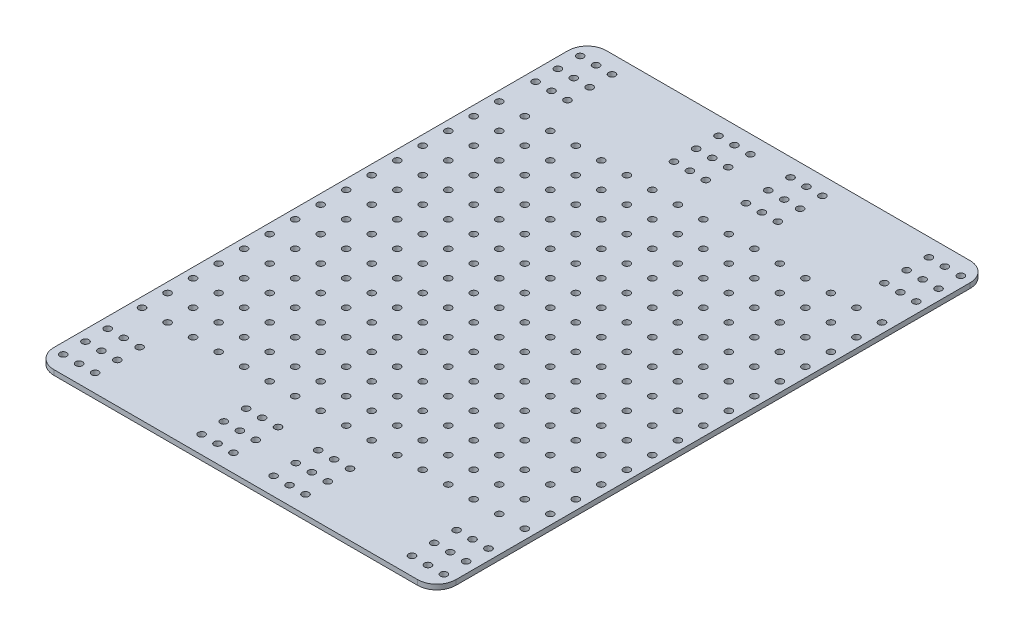
SolidWorks part; units mm, degrees
material "Hexcel AS4C (3000 Filaments)"
ref_plane "Front Plane" through (0, 0, 0) normal (0, 0, 1) x (1, 0, 0)
ref_plane "Top Plane" through (0, 0, 0) normal (0, 1, 0) x (1, 0, 0)
ref_plane "Right Plane" through (0, 0, 0) normal (1, 0, 0) x (0, 0, -1)
sketch "Sketch2" plane through (0, 50, 0) normal (0, 1, 0) x (1, 0, 0)
  line L6 (100.0588, 137.5) -> (-100.0588, 137.5)
  line L7 (100.0588, 137.5) -> (100.0588, -137.5)
  line L8 (100.0588, -137.5) -> (-100.0588, -137.5)
  line L9 (-100.0588, 137.5) -> (-100.0588, -137.5)
  line L10 (100.0588, 137.5) -> (-100.0588, -137.5) construction
  line L11 (100.0588, -137.5) -> (-100.0588, 137.5) construction
  point P0 (0, 0)
extrude "Boss-Extrude1" add sketch "Sketch2" along normal blind 2.5
sketch "Sketch4" plane through (0, 52.5, 0) normal (0, 1, 0) x (1, 0, 0)
  circle A0 centre (-9.9812, -128.65) radius 1.27 construction
  circle A1 centre (-9.9812, -106.4725) radius 1.27 construction
  circle A2 centre (-9.9812, -117.5612) radius 1.27 construction
  circle A3 centre (-17.9187, -117.5612) radius 1.27 construction
  circle A4 centre (-17.9187, -106.4725) radius 1.27 construction
  circle A5 centre (-25.8562, -106.4725) radius 1.27 construction
  circle A6 centre (-25.8562, -117.5612) radius 1.27 construction
  circle A7 centre (-17.9187, -128.65) radius 1.27 construction
  circle A8 centre (-25.8562, -128.65) radius 1.27 construction
  circle A9 centre (-86.8122, -117.5612) radius 1.27 construction
  circle A10 centre (-86.8122, -128.65) radius 1.27 construction
  circle A11 centre (-78.8747, -128.65) radius 1.27 construction
  circle A12 centre (-78.8747, -117.5612) radius 1.27 construction
  circle A13 centre (-78.8747, -106.4725) radius 1.27 construction
  circle A14 centre (-86.8122, -106.4725) radius 1.27 construction
  circle A15 centre (-94.7497, -106.4725) radius 1.27 construction
  circle A16 centre (-94.7497, -117.5612) radius 1.27 construction
  circle A17 centre (-94.7497, -128.65) radius 1.27 construction
  circle A18 centre (-9.9812, -128.65) radius 1.27 construction
  circle A19 centre (-9.9812, -106.4725) radius 1.27 construction
  circle A20 centre (-9.9812, -117.5612) radius 1.27 construction
  circle A21 centre (-17.9187, -117.5612) radius 1.27 construction
  circle A22 centre (-17.9187, -106.4725) radius 1.27 construction
  circle A23 centre (-25.8562, -106.4725) radius 1.27 construction
  circle A24 centre (-25.8562, -117.5612) radius 1.27 construction
  circle A25 centre (-17.9187, -128.65) radius 1.27 construction
  circle A26 centre (-25.8562, -128.65) radius 1.27 construction
  circle A27 centre (-86.8122, -117.5612) radius 1.27 construction
  circle A28 centre (-86.8122, -128.65) radius 1.27 construction
  circle A29 centre (-78.8747, -128.65) radius 1.27 construction
  circle A30 centre (-78.8747, -117.5612) radius 1.27 construction
  circle A31 centre (-78.8747, -106.4725) radius 1.27 construction
  circle A32 centre (-86.8122, -106.4725) radius 1.27 construction
  circle A33 centre (-94.7497, -106.4725) radius 1.27 construction
  circle A34 centre (-94.7497, -117.5612) radius 1.27 construction
  circle A35 centre (-94.7497, -128.65) radius 1.27 construction
hole_wizard "M3 Clearance Hole1" positions "3DSketch2" profile "Sketch6" hole size "M3" standard "ANSI Metric" end condition through all
sketch3d "3DSketch2"
  point P0 (-94.7497, 52.5, 106.4725)
  point P3 (-86.8122, 52.5, 106.4725)
  point P6 (-78.8747, 52.5, 106.4725)
  point P9 (-78.8747, 52.5, 117.5612)
  point P12 (-86.8122, 52.5, 117.5612)
  point P15 (-94.7497, 52.5, 117.5612)
  point P18 (-94.7497, 52.5, 128.65)
  point P21 (-86.8122, 52.5, 128.65)
  point P24 (-78.8747, 52.5, 128.65)
  point P27 (-25.8562, 52.5, 106.4725)
  point P30 (-17.9187, 52.5, 106.4725)
  point P33 (-9.9812, 52.5, 106.4725)
  point P35 (-9.9812, 52.5, 117.5612)
  point P38 (-17.9187, 52.5, 117.5612)
  point P41 (-25.8562, 52.5, 117.5612)
  point P44 (-25.8562, 52.5, 128.65)
  point P47 (-17.9187, 52.5, 128.65)
  point P50 (-9.9812, 52.5, 128.65)
sketch "Sketch6" plane through (-94.7497, 52.5, 106.4725) normal (1, 0, 0) x (0, 0, 1)
  line L0 (0, 0) -> (0, 2.5)
  line L1 (0, 2.5) -> (1.7, 2.5)
  line L2 (1.7, 2.5) -> (1.7, 0)
  line L5 (1.7, 0) -> (0, 0)
  line L11 (0, -6.35) -> (0, 107.95) construction
  dimension "Thru Hole Dia." = 3.4
  dimension "Thru Hole Depth" = 2.5
mirror "Mirror1" about plane through (0, 0, 0) normal (1, 0, 0) of "M3 Clearance Hole1"
mirror "Mirror2" about plane through (0, 0, 0) normal (0, 0, 1) of "M3 Clearance Hole1", "Mirror1"
fillet "Fillet1" radius 9.525 4 edges at (-100.0588, 51.25, -137.5) (100.0588, 51.25, 137.5) (-100.0588, 51.25, 137.5) (100.0588, 51.25, -137.5)
sketch "Sketch7" plane through (0, 52.5, 0) normal (0, 1, 0) x (1, 0, 0)
  line L1 (0, 0) -> (6.35, 0) construction
  line L2 (0, 0) -> (0, -6.35) construction
  line L3 (0, -6.35) -> (6.35, -6.35) construction
  line L4 (6.35, 0) -> (6.35, -6.35) construction
  point P6 (6.35, -6.35)
  dimension "D1" = 6.35
hole_wizard "M3 Clearance Hole2" positions "Sketch9" profile "Sketch10" hole size "M3" standard "ANSI Metric" end condition through all
sketch "Sketch9" plane through (0, 52.5, 0) normal (0, 1, 0) x (1, 0, 0)
  point P0 (6.35, 0)
sketch "Sketch10" plane through (6.35, 52.5, 0) normal (1, 0, 0) x (0, 0, 1)
  line L0 (0, 0) -> (0, 2.5)
  line L1 (0, 2.5) -> (1.7, 2.5)
  line L2 (1.7, 2.5) -> (1.7, 0)
  line L5 (1.7, 0) -> (0, 0)
  line L11 (0, -6.35) -> (0, 107.95) construction
  dimension "Thru Hole Dia." = 3.4
  dimension "Thru Hole Depth" = 2.5
pattern_linear "LPattern1" count 8 spacing 12.7 along (0, 0, 1) count 8 spacing 12.7 along (1, 0, 0) of "M3 Clearance Hole2"
mirror "Mirror3" about plane through (0, 0, 0) normal (0, 0, 1) of "LPattern1", "M3 Clearance Hole2"
mirror "Mirror4" about plane through (0, 0, 0) normal (1, 0, 0) of "Mirror3", "LPattern1", "M3 Clearance Hole2"
